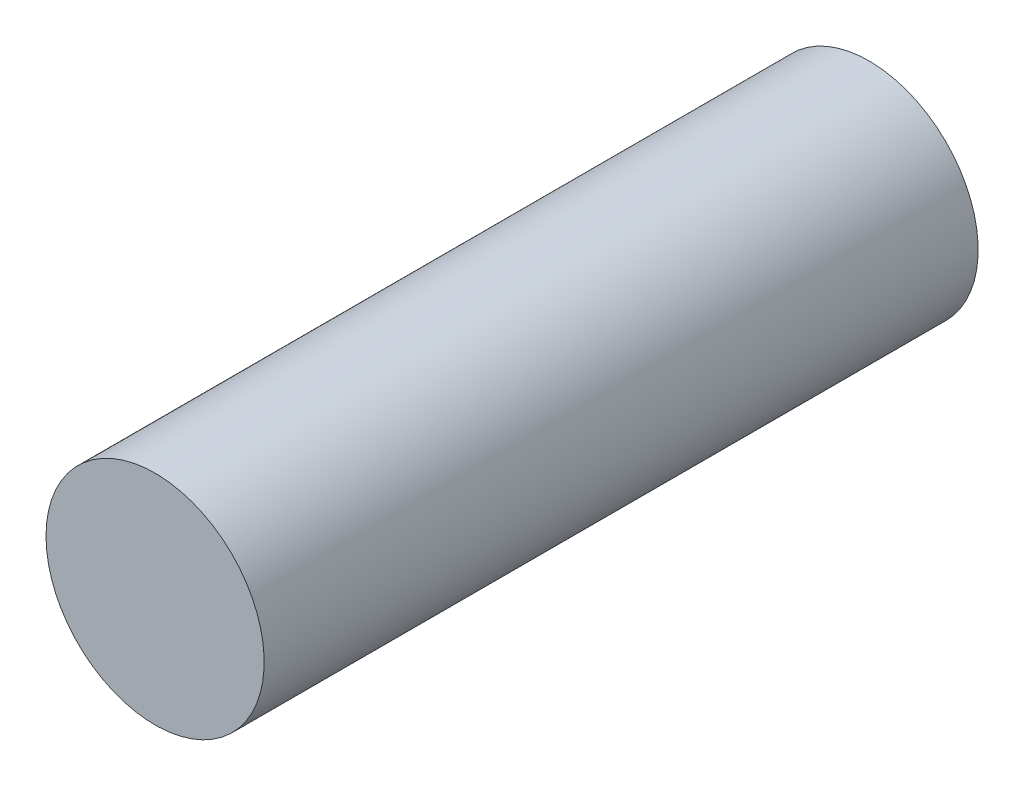
SolidWorks part; units mm, degrees
ref_plane "前视基准面" through (0, 0, 0) normal (0, 0, 1) x (1, 0, 0)
ref_plane "上视基准面" through (0, 0, 0) normal (0, 1, 0) x (1, 0, 0)
ref_plane "右视基准面" through (0, 0, 0) normal (1, 0, 0) x (0, 0, -1)
other "Configuration Table"
sketch "Sketch1" plane through (0, 0, 0) normal (0, 0, 1) x (1, 0, 0)
  circle A0 centre (0, 0) radius 27.5
extrude "Boss-Extrude1" add sketch "Sketch1" along normal blind 180
ref_plane "mount_face_bottom" through (0, 0, 0) normal (0, 0, 1) x (1, 0, 0)
ref_plane "mount_face_top" through (0, 0, 180) normal (0, 0, 1) x (1, 0, 0)
sketch3d "3DSketch1"
  line L0 (0, 0, 0) -> (0, 0, 180) construction
ref_axis "main_axis_z" through (0, 0, 0) along (0, 0, 1)
sketch "Sketch2" plane through (0, 0, 0) normal (0, 0, 1) x (1, 0, 0)
  circle A0 centre (0, 0) radius 27.5
extrude "Boss-Extrude2" add sketch "Sketch2" along normal blind 180
ref_plane "Plane3" through (0, 0, 0) normal (0, 0, 1) x (1, 0, 0)
ref_plane "Plane4" through (0, 0, 180) normal (0, 0, 1) x (1, 0, 0)
sketch3d "3DSketch2"
  line L0 (0, 0, 0) -> (0, 0, 180) construction
ref_axis "Axis2" through (0, 0, 0) along (0, 0, 1)
sketch "Sketch3" plane through (0, 0, 0) normal (0, 0, 1) x (1, 0, 0)
  circle A0 centre (0, 0) radius 27.5
extrude "Boss-Extrude3" add sketch "Sketch3" along normal blind 180
ref_plane "Plane5" through (0, 0, 0) normal (0, 0, 1) x (1, 0, 0)
ref_plane "Plane6" through (0, 0, 180) normal (0, 0, 1) x (1, 0, 0)
sketch3d "3DSketch3"
  line L0 (0, 0, 0) -> (0, 0, 180) construction
ref_axis "Axis3" through (0, 0, 0) along (0, 0, 1)
